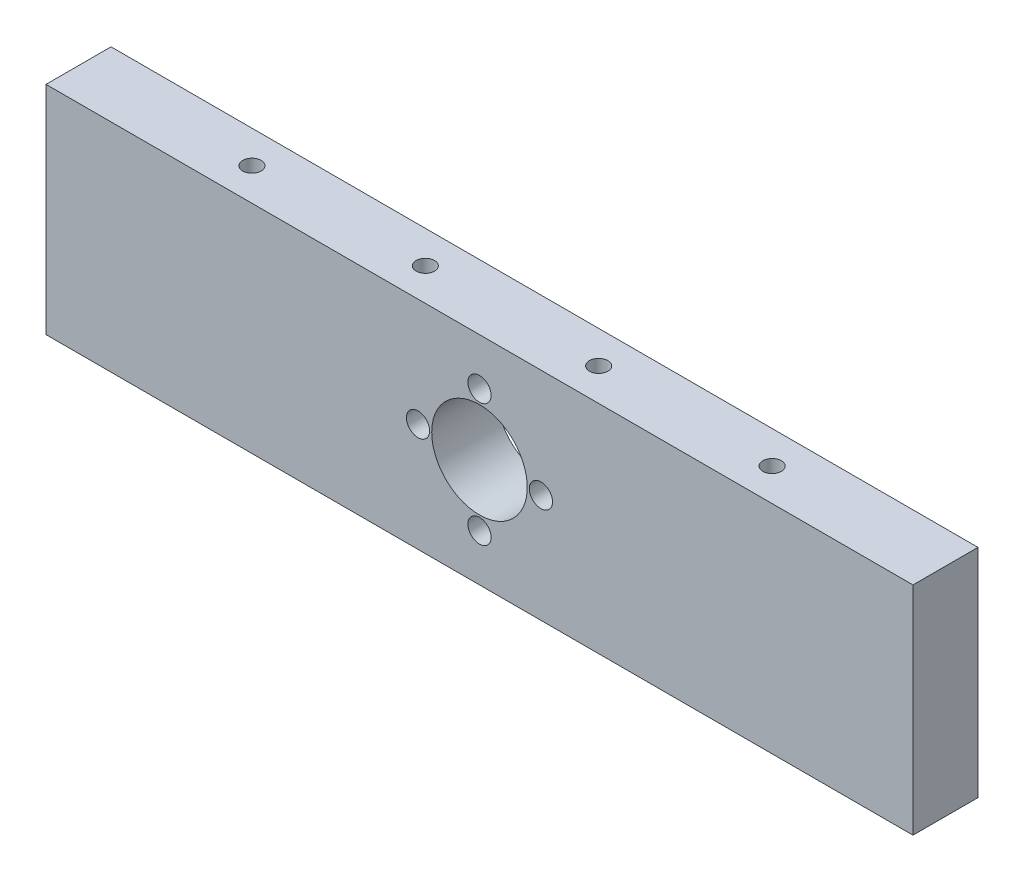
SolidWorks part; units mm, degrees
material "PE High Density Film"
ref_plane "Front Plane" through (0, 0, 0) normal (0, 0, 1) x (1, 0, 0)
ref_plane "Top Plane" through (0, 0, 0) normal (0, 1, 0) x (1, 0, 0)
ref_plane "Right Plane" through (0, 0, 0) normal (1, 0, 0) x (0, 0, -1)
sketch "Sketch1" plane through (0, 0, 0) normal (0, 0, 1) x (1, 0, 0)
  line L0 (-1.1838, 11.4734) -> (-11.4734, 1.1838) construction
  line L1 (-63.5, 15.875) -> (63.5, 15.875)
  line L2 (-63.5, 15.875) -> (-63.5, -15.875)
  line L3 (-63.5, -15.875) -> (63.5, -15.875)
  line L4 (63.5, 15.875) -> (63.5, -15.875)
  line L5 (-63.5, 15.875) -> (63.5, -15.875) construction
  line L6 (-63.5, -15.875) -> (63.5, 15.875) construction
  line L7 (-11.4734, -1.1838) -> (-1.1838, -11.4734) construction
  line L8 (1.1838, -11.4734) -> (11.4734, -1.1838) construction
  line L9 (11.4734, 1.1838) -> (1.1838, 11.4734) construction
  line L10 (0, 0) -> (0, 15.875) construction
  circle A0 centre (0, -9) radius 1.7
  circle A1 centre (-9, 0) radius 1.7
  circle A2 centre (0, 9) radius 1.7
  circle A3 centre (9, 0) radius 1.7
  arc A4 (-11.4734, 1.1838) -> (-11.677, 0.7327) centre (-10.9784, 0.6889) ccw construction
  arc A5 (-11.677, 0.7327) -> (-11.677, -0.7327) centre (0, 0) ccw construction
  arc A6 (-11.677, -0.7327) -> (-11.4734, -1.1838) centre (-10.9784, -0.6889) ccw construction
  arc A7 (-1.1838, -11.4734) -> (-0.7327, -11.677) centre (-0.6889, -10.9784) ccw construction
  arc A8 (-0.7327, -11.677) -> (0.7327, -11.677) centre (0, 0) ccw construction
  arc A9 (0.7327, -11.677) -> (1.1838, -11.4734) centre (0.6889, -10.9784) ccw construction
  arc A10 (11.4734, -1.1838) -> (11.677, -0.7327) centre (10.9784, -0.6889) ccw construction
  arc A11 (11.677, -0.7327) -> (11.677, 0.7327) centre (0, 0) ccw construction
  arc A12 (11.677, 0.7327) -> (11.4734, 1.1838) centre (10.9784, 0.6889) ccw construction
  arc A13 (1.1838, 11.4734) -> (0.7327, 11.677) centre (0.6889, 10.9784) ccw construction
  arc A14 (0.7327, 11.677) -> (-0.7327, 11.677) centre (0, 0) ccw construction
  arc A15 (-0.7327, 11.677) -> (-1.1838, 11.4734) centre (-0.6889, 10.9784) ccw construction
  circle A16 centre (0, 0) radius 7
  point P0 (0, 0)
  dimension "D3" = 3.4
  dimension "D6" = 14
  dimension "D1" = 127
  dimension "D2" = 31.75
  dimension "D4" = 14.5516
  dimension "D5" = 90
  dimension "D7" = 15.875
extrude "Boss-Extrude1" add sketch "Sketch1" along normal blind 9.525
hole_wizard "Tap Drill for #6-32 Tap1" positions "Sketch11" profile "Sketch12" hole size "#6-32" standard "ANSI Inch"
sketch "Sketch11" plane through (0, -15.875, 0) normal (0, -1, 0) x (-1, 0, 0)
  line L0 (-63.5, -9.525) -> (-63.5, 0) construction
  line L1 (63.5, -9.525) -> (-63.5, -9.525) construction
  point P0 (-38.1, -4.7625)
  dimension "D1" = 25.4
  dimension "D2" = 4.7625
sketch "Sketch12" plane through (38.1, -15.875, 4.7625) normal (1, 0, 0) x (0, 0, -1)
  line L0 (0, 0) -> (0, 13.5127)
  line L1 (0, 13.5127) -> (1.3525, 12.7)
  line L2 (1.3525, 12.7) -> (1.3525, 0)
  line L5 (1.3525, 0) -> (0, 0)
  line L10 (0, 13.5127) -> (-1.3526, 12.7) construction
  line L11 (0, -6.35) -> (0, 107.95) construction
  dimension "Hole Dia." = 2.7051
  dimension "Hole Depth" = 12.7
  dimension "Drill Angle" = 118
pattern_linear "LPattern1" count 4 spacing 25.4 along (-1, 0, 0) of "Tap Drill for #6-32 Tap1"
mirror "Mirror8" about plane through (0, 0, 0) normal (0, 1, 0) of "Tap Drill for #6-32 Tap1", "LPattern1"
equation "\"Plate Screw Hole Diameter\"= 0.116in"
equation "\"Plate Width\"= 5in"
equation "\"Plate Thickness\"= .375in"
equation "\"Num holes\"= 4"
equation "\"D1@Sketch1\"= \"Plate Width\""
equation "\"Plate Height\"= 1.25in"
equation "\"D2@Sketch1\"= \"Plate Height\""
equation "\"D1@Sketch11\"=\"Plate Width\" / ( \"Num holes\" + 1)"
equation "\"D2@Sketch11\"=\"Plate Thickness\"/2"
equation "\"D3@LPattern1\"=\"Plate Width\" / ( \"Num holes\"  + 1 )"
